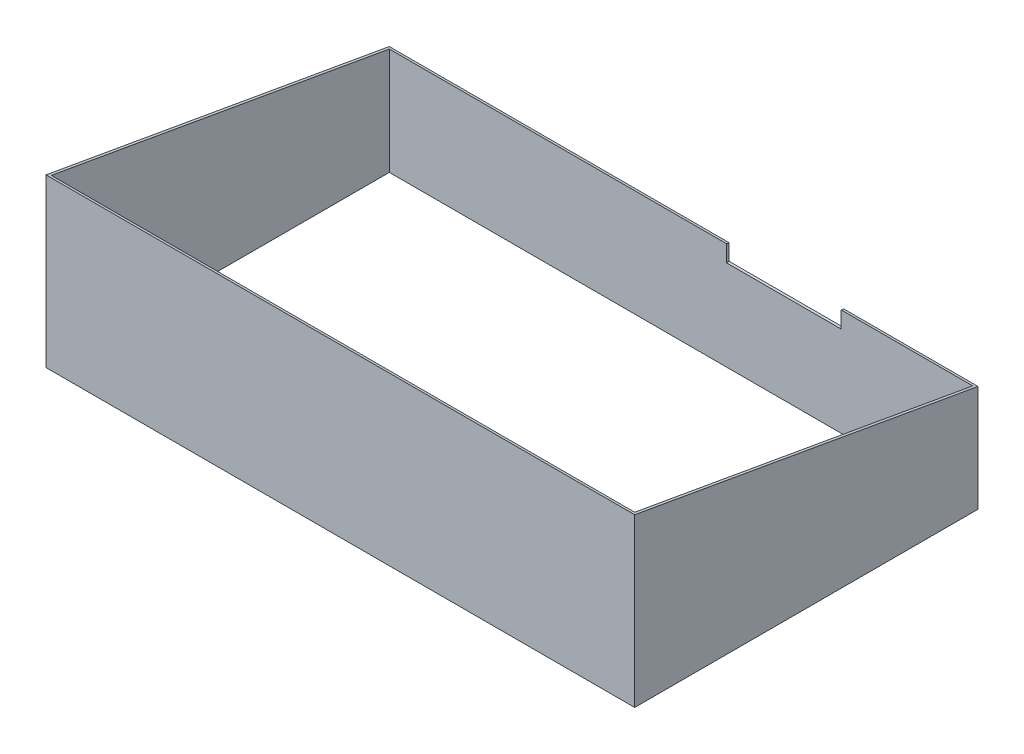
SolidWorks part; units mm, degrees
material "Particle Board"
ref_plane "Front Plane" through (0, 0, 0) normal (0, 0, 1) x (1, 0, 0)
ref_plane "Top Plane" through (0, 0, 0) normal (0, 1, 0) x (1, 0, 0)
ref_plane "Right Plane" through (0, 0, 0) normal (1, 0, 0) x (0, 0, -1)
sketch "Sketch1" plane through (0, 0, 0) normal (1, 0, 0) x (0, 0, -1)
  line L0 (0, 403.2291) -> (0, 0)
  line L1 (0, 0) -> (829.3066, 0)
  line L4 (829.3066, 0) -> (829.3066, 257)
  line L5 (0, 403.2291) -> (829.3066, 257)
  dimension "D1" = 10
  dimension "D2" = 842.1
  dimension "D3" = 257
extrude "Boss-Extrude1" add sketch "Sketch1" along normal blind 710.99 and the other way blind 710.99
shell "Shell1" thickness 6.35 removed face at (0, 0, -414.6533) removed face at (0, 330.1146, -414.6533)
sketch "Sketch3" plane through (0, 0, -822.9566) normal (0, 0, 1) x (1, 0, 0)
  line L1 (109.99, 268.1197) -> (386.99, 268.1197)
  line L2 (109.99, 268.1197) -> (109.99, 218.1197)
  line L3 (109.99, 218.1197) -> (386.99, 218.1197)
  line L4 (386.99, 268.1197) -> (386.99, 218.1197)
  line L5 (704.64, 258.1197) -> (-704.64, 258.1197) construction
  line L7 (0, -221.776) -> (0, 221.776) construction
  dimension "D1" = 109.99
  dimension "D2" = 277
  dimension "D3" = 10
  dimension "D4" = 40
extrude "Cut-Extrude2" cut sketch "Sketch3" against normal up to next
sketch "Sketch4" plane through (-710.99, 0, 0) normal (-1, 0, 0) x (0, 0, 1)
  line L1 (-158.5, 32) -> (-251.5, 32)
  line L2 (-158.5, 32) -> (-158.5, 134)
  line L3 (-158.5, 134) -> (-251.5, 134)
  line L4 (-251.5, 32) -> (-251.5, 134)
  dimension "D1" = 93
  dimension "D2" = 102
  dimension "D3" = 158.5
  dimension "D4" = 32
extrude "Cut-Extrude3" cut sketch "Sketch4" against normal up to next
